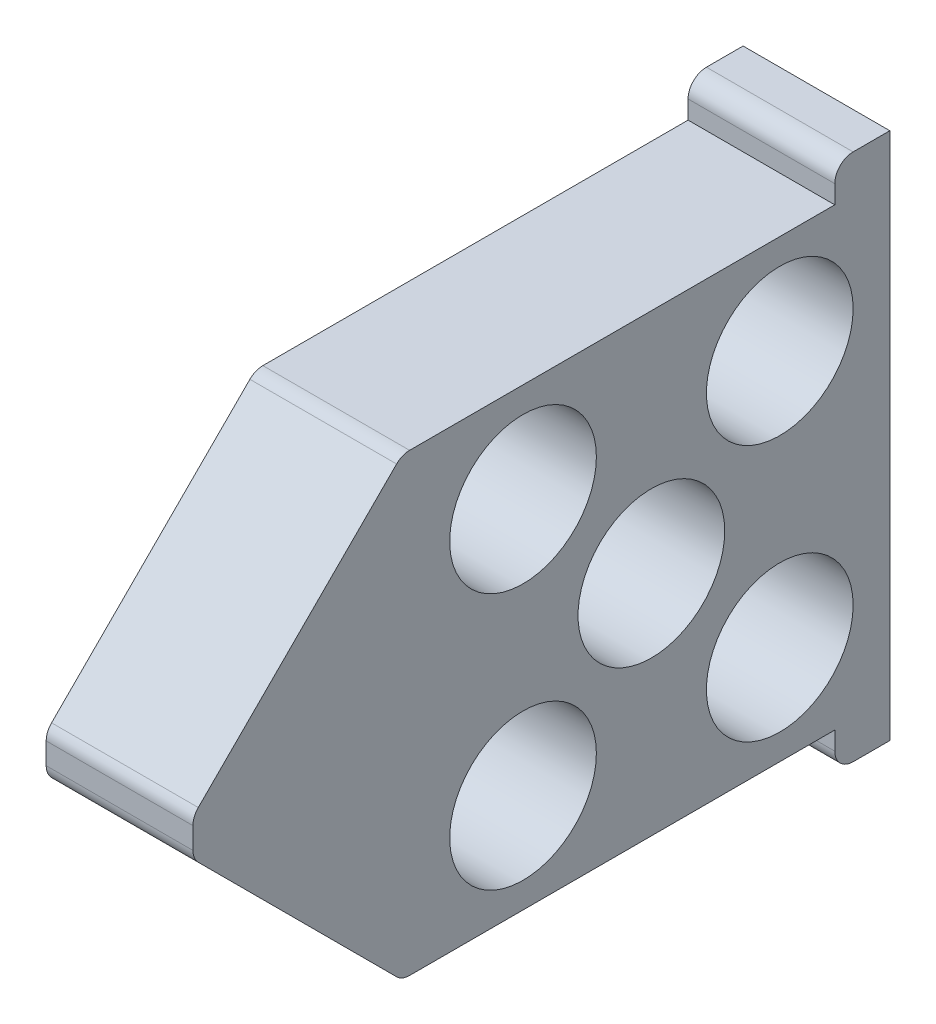
SolidWorks part; units mm, degrees
ref_plane "Front Plane" through (0, 0, 0) normal (0, 0, 1) x (1, 0, 0)
ref_plane "Top Plane" through (0, 0, 0) normal (0, 1, 0) x (1, 0, 0)
ref_plane "Right Plane" through (0, 0, 0) normal (1, 0, 0) x (0, 0, -1)
sketch "Sketch1" plane through (0, 0, 0) normal (1, 0, 0) x (0, 0, -1)
  line L0 (-6, 6.2) -> (6, -6.2) construction
  line L2 (-6, 6.2) -> (-6, -6.2) construction
  line L3 (-5.8, 6.2) -> (-11.5, 0.5)
  line L4 (6, 6.2) -> (6, -6.2) construction
  line L5 (6, 6.2) -> (6, 7.2)
  line L6 (6, 7.2) -> (7.5, 7.2)
  line L7 (7.5, 7.2) -> (7.5, -7.2)
  line L8 (-4.2787, 0) -> (7.198, 0) construction
  line L9 (6, -6.2) -> (6, -7.2)
  line L10 (6, -7.2) -> (7.5, -7.2)
  line L11 (6, 6.2) -> (-5.8, 6.2)
  line L12 (-11.5, 6.2) -> (-11.5, -6.2) construction
  line L13 (-11.5, 0.5) -> (-11.5, -0.5)
  line L14 (-5.8, -6.2) -> (-11.5, -0.5)
  line L15 (6, -6.2) -> (-5.8, -6.2)
  point P4 (0, 0)
  point P13 (7.5, 0)
  point P16 (-11.5, 0)
  point P18 (-11.5, 0)
  point P20 (0, 0)
  point P21 (-2.1924, 4)
  point P22 (-7.7226, 1.0439)
  point P23 (-22.6378, 0.5)
  dimension "D1" = 5.7
  dimension "D2" = 1
  dimension "D3" = 1.5
  dimension "D4" = 1
  dimension "D5" = 17.5
  dimension "D6" = 45
  dimension "D7" = 0.2
extrude "Boss-Extrude1" add sketch "Sketch1" along normal blind 4
fillet "Fillet1" [suppressed] radius 2
fillet "Fillet2" radius 0.5 6 edges at (2, -7.2, -6) (2, 7.2, -6) (2, -6.2, 5.8) (2, -0.5, 11.5) (2, 0.5, 11.5) (2, 6.2, 5.8)
chamfer "Chamfer1" [suppressed] distance 1.9 angle 50
hole_wizard "Ø4.0mm mass reduction holes" positions "Sketch2" profile "Sketch3" hole size "Ø4.0" standard "ANSI Metric"
sketch "Sketch2" plane through (4, 0, 0) normal (1, 0, 0) x (0, 0, -1)
  line L1 (-2.5, 3.5) -> (4.5, 3.5) construction
  line L2 (-2.5, 3.5) -> (-2.5, -3.5) construction
  line L3 (-2.5, -3.5) -> (4.5, -3.5) construction
  line L4 (4.5, 3.5) -> (4.5, -3.5) construction
  line L5 (-2.5, 3.5) -> (4.5, -3.5) construction
  line L6 (-2.5, -3.5) -> (4.5, 3.5) construction
  line L7 (1, 0) -> (0, 0) construction
  point P0 (4.5, -3.5)
  point P2 (4.5, 3.5)
  point P4 (-2.5, -3.5)
  point P6 (-2.5, 3.5)
  point P8 (1, 0)
  point P60 (1, 0)
  point P65 (0, 0)
  dimension "D1" = 7
  dimension "D2" = 7
  dimension "D3" = 1
sketch "Sketch3" plane through (4, -3.5, -4.5) normal (0, 1, 0) x (0, 0, -1)
  line L0 (0, 0) -> (0, 10.7267)
  line L1 (0, 10.7267) -> (2, 9.525)
  line L2 (2, 9.525) -> (2, 0)
  line L5 (2, 0) -> (0, 0)
  line L10 (0, 10.7267) -> (-2, 9.525) construction
  line L11 (0, -6.35) -> (0, 107.95) construction
  dimension "Hole Dia." = 4
  dimension "Hole Depth" = 9.525
  dimension "Drill Angle" = 118
